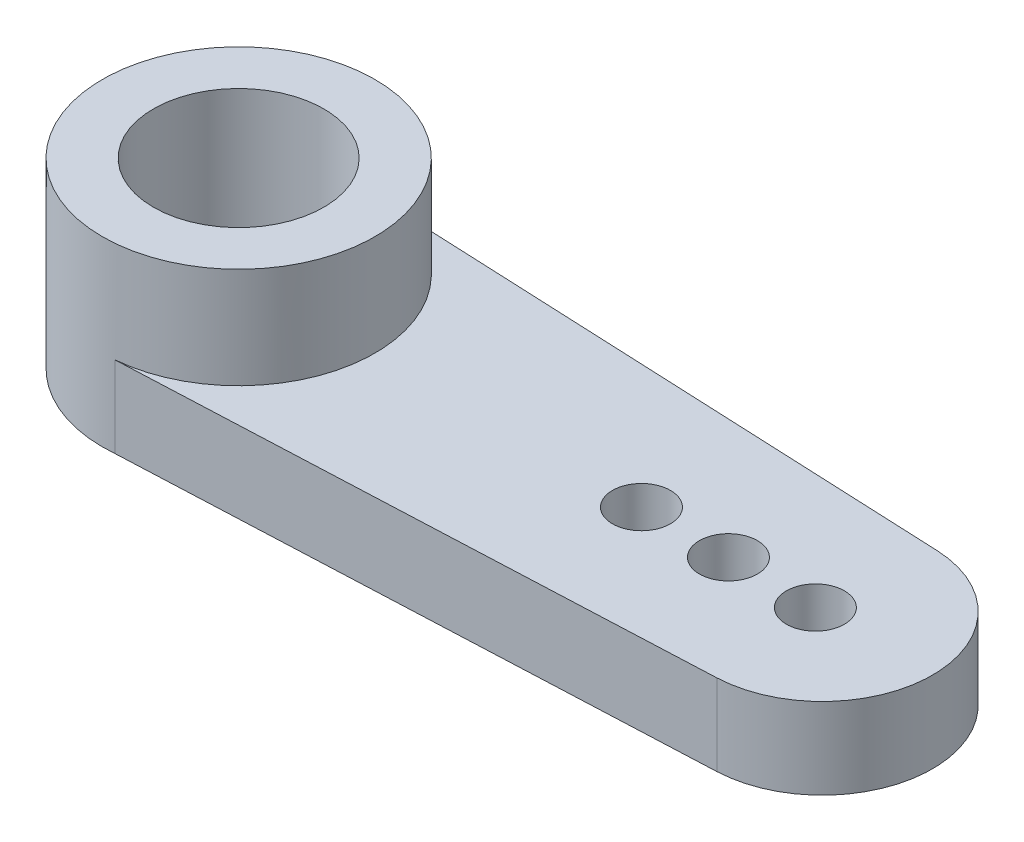
SolidWorks part; units mm, degrees
material "Servo Horn"
ref_plane "Front Plane" through (0, 0, 0) normal (0, 0, 1) x (1, 0, 0)
ref_plane "Top Plane" through (0, 0, 0) normal (0, 1, 0) x (1, 0, 0)
ref_plane "Right Plane" through (0, 0, 0) normal (1, 0, 0) x (0, 0, -1)
sketch "Sketch1" plane through (0, 0, 0) normal (0, 1, 0) x (1, 0, 0)
  circle A0 centre (0, 0) radius 2.9845
  circle A1 centre (0, 0) radius 1.8669
  dimension "D1" = 5.969
  dimension "D2" = 3.7338
extrude "Boss-Extrude1" add sketch "Sketch1" along normal blind 3.9878
sketch "Sketch2" plane through (0, 0, 0) normal (0, -1, 0) x (1, 0, 0)
  line L0 (0, 2.9845) -> (12.8905, 2.413)
  line L1 (0, -2.9845) -> (12.8905, -2.413)
  line L2 (-2.9845, 0) -> (-2.9845, 9.9842) construction
  circle A0 centre (0, 0) radius 2.9845 construction
  arc A1 (12.8905, 2.413) -> (12.8905, -2.413) centre (12.7835, 0) cw
  arc A2 (0, -2.9845) -> (0, 2.9845) centre (0, 0) ccw
  circle M1 centre (0, 0) radius 2.9845
  dimension "D2" = 4.826
  dimension "D1" = 15.875
extrude "Boss-Extrude2" add sketch "Sketch2" against normal blind 1.778 contours A1 L0 L1 M1 region at (8.3259, 0, 0)
sketch "Sketch3" plane through (0, 0, 0) normal (0, -1, 0) x (1, 0, 0)
  line L0 (11.3635, 0) -> (11.3635, 1.9948) construction
  line L1 (11.9985, 0) -> (11.9985, 1.7434) construction
  line L2 (10.0935, 0) -> (10.0935, 1.6934) construction
  line L3 (9.4585, 0) -> (9.4585, 1.9948) construction
  circle A0 centre (8.8235, 0) radius 0.635
  circle A1 centre (10.7285, 0) radius 0.635
  circle A2 centre (12.6335, 0) radius 0.635
  arc A3 (12.8905, -2.413) -> (12.8905, 2.413) centre (12.7835, 0) ccw construction
  point P15 (15.1989, 0)
  dimension "D1" = 1.27
  dimension "D2" = 0.635
  dimension "D3" = 0.635
  dimension "D4" = 5.7404
extrude "Cut-Extrude1" cut sketch "Sketch3" against normal through all
